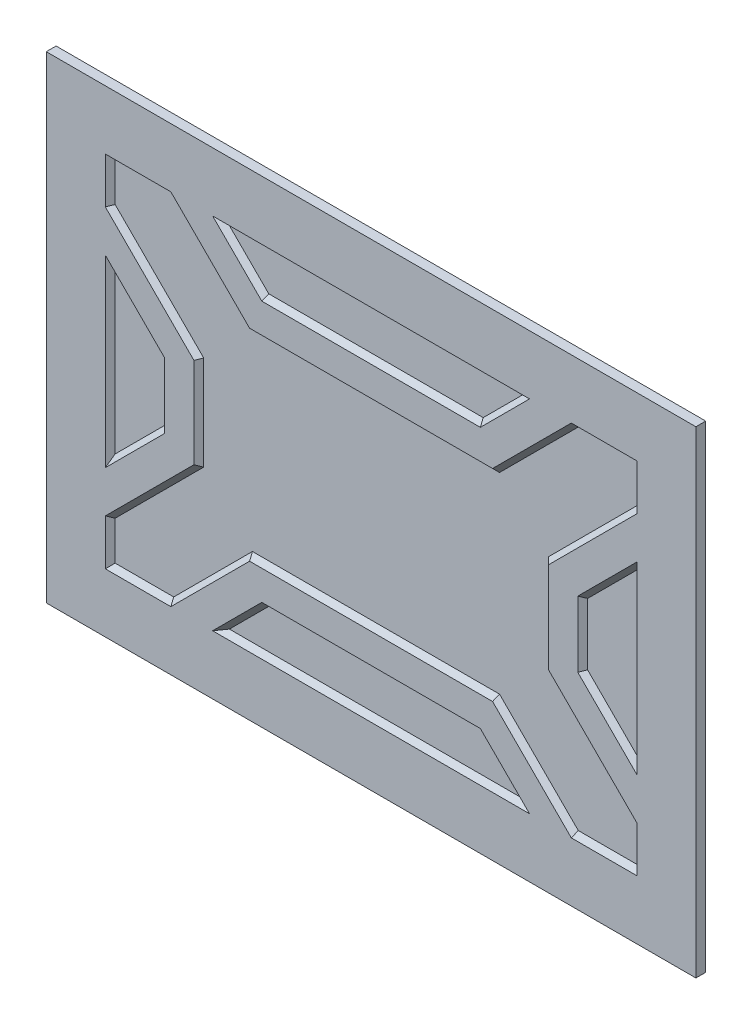
SolidWorks part; units mm, degrees
ref_plane "Plan de face" through (0, 0, 0) normal (0, 0, 1) x (1, 0, 0)
ref_plane "Plan de dessus" through (0, 0, 0) normal (0, 1, 0) x (1, 0, 0)
ref_plane "Plan de droite" through (0, 0, 0) normal (1, 0, 0) x (0, 0, -1)
sketch "Esquisse1" plane through (0, 0, 0) normal (0, 0, 1) x (1, 0, 0)
  line L1 (0, 0) -> (660, 0)
  line L2 (0, 0) -> (0, 485)
  line L3 (0, 485) -> (660, 485)
  line L4 (660, 0) -> (660, 485)
  dimension "D1" = 485
  dimension "D2" = 660
extrude "Boss.-Extru.1" add sketch "Esquisse1" along normal blind 10
sketch "Esquisse2" plane through (0, 0, 10) normal (0, 0, 1) x (1, 0, 0)
  line L0 (206.5685, 345) -> (150, 288.4315) construction
  line L1 (120, 208.9949) -> (120, 276.0051)
  line L2 (120, 276.0051) -> (60, 336.0051)
  line L3 (218.9949, 375) -> (441.0051, 375)
  line L4 (330, 425) -> (330, 60) construction
  line L5 (600, 242.5) -> (60, 242.5) construction
  line L6 (60, 425) -> (60, 378.4315)
  line L7 (60, 378.4315) -> (150, 288.4315)
  line L8 (60, 425) -> (60, 60)
  line L9 (60, 60) -> (600, 60)
  line L10 (600, 60) -> (600, 425)
  line L11 (600, 425) -> (60, 425)
  line L12 (60, 425) -> (60, 60) construction
  line L13 (60, 60) -> (600, 60) construction
  line L14 (600, 60) -> (600, 425) construction
  line L15 (600, 425) -> (60, 425) construction
  line L16 (150, 288.4315) -> (150, 196.5685)
  line L17 (60, 425) -> (126.5685, 425)
  line L18 (126.5685, 425) -> (206.5685, 345)
  line L19 (453.4315, 345) -> (206.5685, 345)
  line L20 (491.0051, 425) -> (168.9949, 425)
  line L21 (168.9949, 425) -> (218.9949, 375)
  line L22 (510, 288.4315) -> (510, 196.5685)
  line L23 (60, 336.0051) -> (60, 148.9949)
  line L24 (540, 208.9949) -> (540, 276.0051)
  line L25 (150, 288.4315) -> (150, 345) construction
  line L26 (150, 345) -> (206.5685, 345) construction
  line L27 (540, 276.0051) -> (600, 336.0051)
  line L28 (600, 336.0051) -> (600, 148.9949)
  line L29 (600, 378.4315) -> (510, 288.4315)
  line L30 (600, 425) -> (600, 378.4315)
  line L31 (600, 425) -> (533.4315, 425)
  line L32 (533.4315, 425) -> (453.4315, 345)
  line L33 (491.0051, 425) -> (441.0051, 375)
  line L34 (120, 208.9949) -> (60, 148.9949)
  line L35 (60, 106.5685) -> (150, 196.5685)
  line L36 (600, 60) -> (533.4315, 60)
  line L37 (600, 60) -> (600, 106.5685)
  line L38 (60, 60) -> (60, 106.5685)
  line L39 (60, 60) -> (126.5685, 60)
  line L40 (491.0051, 60) -> (168.9949, 60)
  line L41 (218.9949, 110) -> (441.0051, 110)
  line L42 (453.4315, 140) -> (206.5685, 140)
  line L43 (168.9949, 60) -> (218.9949, 110)
  line L44 (126.5685, 60) -> (206.5685, 140)
  line L45 (491.0051, 60) -> (441.0051, 110)
  line L46 (533.4315, 60) -> (453.4315, 140)
  line L47 (600, 106.5685) -> (510, 196.5685)
  line L48 (540, 208.9949) -> (600, 148.9949)
  point P20 (330, 345)
  point P23 (510, 242.5)
  point P31 (330, 375)
  point P33 (120, 242.5)
  point P34 (150, 242.5)
  point P47 (540, 242.5)
  dimension "D2" = 90
  dimension "D3" = 80
  dimension "D4" = 80
  dimension "D5" = 45
  dimension "D6" = 30
  dimension "D7" = 30
  dimension "D8" = 30
  dimension "D9" = 30
  dimension "D1" = 60
extrude "Enlèv. mat.-Extru.1" cut sketch "Esquisse2" against normal blind 5
chamfer "Chanfrein1" distance 5 angle 45 36 edges at (330, 60, 5) (193.9949, 85, 5) (330, 110, 5) (466.0051, 85, 5) (60, 242.5, 5) (90, 306.0051, 5) (120, 242.5, 5) (90, 178.9949, 5) (600, 242.5, 5) (570, 178.9949, 5) (540, 242.5, 5) (570, 306.0051, 5) (166.5685, 385, 5) (330, 345, 5) (493.4315, 385, 5) (566.7157, 425, 5) (600, 401.7157, 5) (555, 333.4315, 5) (510, 242.5, 5) (555, 151.5685, 5) (600, 83.2843, 5) (566.7157, 60, 5) (493.4315, 100, 5) (330, 140, 5) (166.5685, 100, 5) (93.2843, 60, 5) (60, 83.2843, 5) (105, 151.5685, 5) (150, 242.5, 5) (105, 333.4315, 5) (60, 401.7157, 5) (93.2843, 425, 5) (330, 425, 5) (466.0051, 400, 5) (330, 375, 5) (193.9949, 400, 5)
